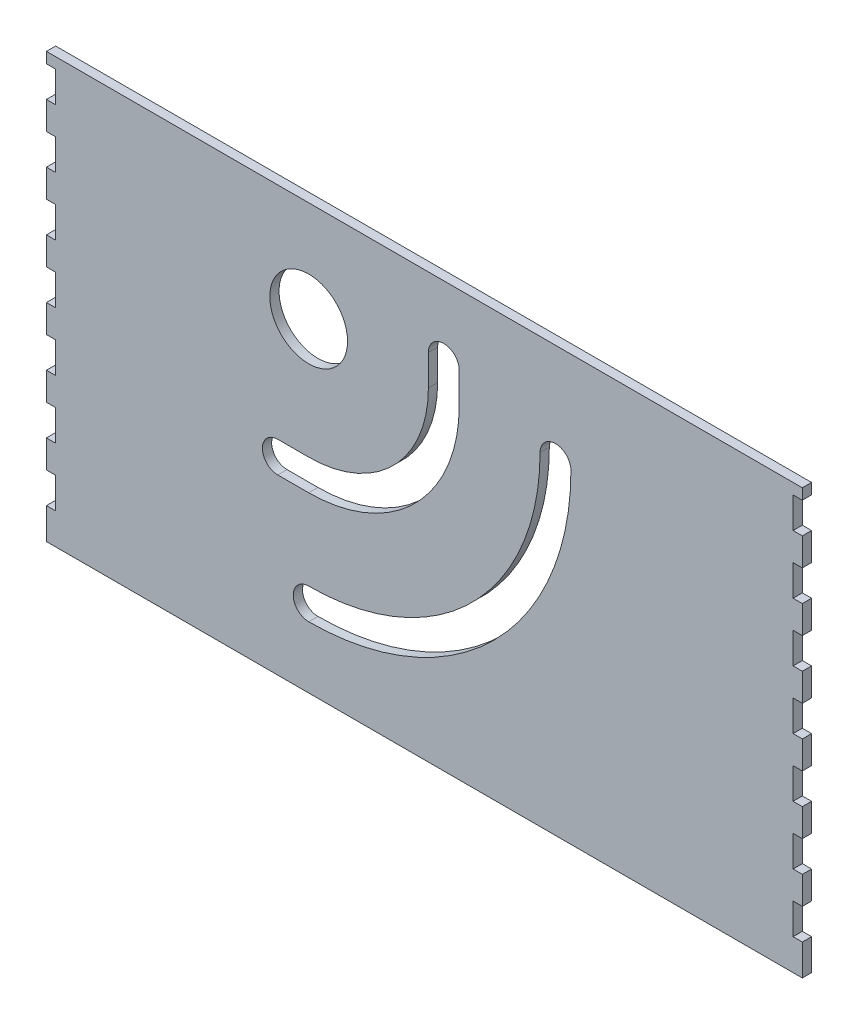
SolidWorks part; units mm, degrees
material "birch 3mm plywood"
ref_plane "Front Plane" through (0, 0, 0) normal (0, 0, 1) x (1, 0, 0)
ref_plane "Top Plane" through (0, 0, 0) normal (0, 1, 0) x (1, 0, 0)
ref_plane "Right Plane" through (0, 0, 0) normal (1, 0, 0) x (0, 0, -1)
sketch "Sketch1" plane through (0, 0, 0) normal (0, 0, 1) x (1, 0, 0)
  line L0 (244.5, 137.6) -> (244.5, 134.1)
  line L1 (-0.5, 137.6) -> (244.5, 137.6)
  line L2 (-0.5, 137.6) -> (-0.5, 0) construction
  line L3 (-0.5, 0) -> (244.5, 0)
  line L4 (244.5, 137.6) -> (244.5, 0) construction
  line L5 (84.5, 59.75) -> (84.5, -77.75) construction
  line L6 (244.5, 134.1) -> (241.5, 134.1)
  line L7 (241.5, 134.1) -> (241.5, 124.1)
  line L8 (241.5, 124.1) -> (244.5, 124.1)
  line L9 (244.5, 124.1) -> (244.5, 115.1)
  line L10 (244.5, 105.1) -> (244.5, 96.1)
  line L11 (241.5, 115.1) -> (241.5, 105.1)
  line L12 (241.5, 105.1) -> (244.5, 105.1)
  line L13 (244.5, 115.1) -> (241.5, 115.1)
  line L14 (244.5, 86.1) -> (244.5, 77.1)
  line L15 (241.5, 96.1) -> (241.5, 86.1)
  line L16 (241.5, 86.1) -> (244.5, 86.1)
  line L17 (244.5, 96.1) -> (241.5, 96.1)
  line L18 (244.5, 67.1) -> (244.5, 58.1)
  line L19 (241.5, 77.1) -> (241.5, 67.1)
  line L20 (241.5, 67.1) -> (244.5, 67.1)
  line L21 (244.5, 77.1) -> (241.5, 77.1)
  line L22 (244.5, 48.1) -> (244.5, 39.1)
  line L23 (241.5, 58.1) -> (241.5, 48.1)
  line L24 (241.5, 48.1) -> (244.5, 48.1)
  line L25 (244.5, 58.1) -> (241.5, 58.1)
  line L26 (244.5, 29.1) -> (244.5, 20.1)
  line L27 (241.5, 39.1) -> (241.5, 29.1)
  line L28 (241.5, 29.1) -> (244.5, 29.1)
  line L29 (244.5, 39.1) -> (241.5, 39.1)
  line L30 (244.5, 10.1) -> (244.5, 0)
  line L31 (241.5, 20.1) -> (241.5, 10.1)
  line L32 (241.5, 10.1) -> (244.5, 10.1)
  line L33 (244.5, 20.1) -> (241.5, 20.1)
  line L34 (122, 137.6) -> (122, 0) construction
  line L35 (-0.5, 10.1) -> (-0.5, 0)
  line L36 (-0.5, 20.1) -> (2.5, 20.1)
  line L37 (2.5, 10.1) -> (-0.5, 10.1)
  line L38 (2.5, 20.1) -> (2.5, 10.1)
  line L39 (-0.5, 39.1) -> (2.5, 39.1)
  line L40 (2.5, 29.1) -> (-0.5, 29.1)
  line L41 (2.5, 39.1) -> (2.5, 29.1)
  line L42 (-0.5, 29.1) -> (-0.5, 20.1)
  line L43 (-0.5, 58.1) -> (2.5, 58.1)
  line L44 (2.5, 48.1) -> (-0.5, 48.1)
  line L45 (2.5, 58.1) -> (2.5, 48.1)
  line L46 (-0.5, 48.1) -> (-0.5, 39.1)
  line L47 (-0.5, 77.1) -> (2.5, 77.1)
  line L48 (2.5, 67.1) -> (-0.5, 67.1)
  line L49 (2.5, 77.1) -> (2.5, 67.1)
  line L50 (-0.5, 67.1) -> (-0.5, 58.1)
  line L51 (-0.5, 96.1) -> (2.5, 96.1)
  line L52 (2.5, 86.1) -> (-0.5, 86.1)
  line L53 (2.5, 96.1) -> (2.5, 86.1)
  line L54 (-0.5, 86.1) -> (-0.5, 77.1)
  line L55 (-0.5, 115.1) -> (2.5, 115.1)
  line L56 (2.5, 105.1) -> (-0.5, 105.1)
  line L57 (2.5, 115.1) -> (2.5, 105.1)
  line L58 (-0.5, 105.1) -> (-0.5, 96.1)
  line L59 (-0.5, 124.1) -> (-0.5, 115.1)
  line L60 (2.5, 124.1) -> (-0.5, 124.1)
  line L61 (2.5, 134.1) -> (2.5, 124.1)
  line L62 (-0.5, 134.1) -> (2.5, 134.1)
  line L63 (-0.5, 137.6) -> (-0.5, 134.1)
  line L64 (93.4095, 96.0905) -> (137.533, 51.967) construction
  line L65 (111.9357, 77.5643) -> (119.0068, 70.4932) construction
  line L66 (123.3, 105) -> (123.3, 115)
  line L68 (133.3, 115) -> (133.3, 105)
  line L69 (84.5, 66.2) -> (74.5, 66.2)
  line L71 (74.5, 56.2) -> (84.5, 56.2)
  arc A0 (84.5, 66.2) -> (123.3, 105) centre (84.5, 105) ccw
  arc A1 (84.5, 56.2) -> (133.3, 105) centre (84.5, 105) ccw
  arc A3 (169.5, 105) -> (159.5, 105) centre (164.5, 105) ccw
  arc A4 (159.5, 105) -> (84.5, 30) centre (84.5, 105) cw
  arc A5 (169.5, 105) -> (84.5, 20) centre (84.5, 105) cw
  arc A6 (84.5, 20) -> (84.5, 30) centre (84.5, 25) cw
  circle A7 centre (84.5, 105) radius 12.6
  arc A8 (123.3, 115) -> (133.3, 115) centre (128.3, 115) cw
  arc A9 (74.5, 56.2) -> (74.5, 66.2) centre (74.5, 61.2) cw
  point P77 (137.533, 51.967)
  point P80 (115.4713, 74.0287)
  point P89 (0, 0)
  point P90 (133.3, 120.0897)
  point P91 (133.3, 116.1836)
  point P92 (133.3, 114.8816)
  dimension "D1" = 10
  dimension "D2" = 75
  dimension "D3" = 20
  dimension "D7" = 25.2
  dimension "D15" = 10
  dimension "D4" = 20
  dimension "D5" = 85
  dimension "D6" = 160
  dimension "D8" = 3.5
  dimension "D9" = 10
  dimension "D10" = 9
  dimension "D12" = 3
  dimension "D13" = 10
  dimension "D14" = 5
  dimension "D11" = 7
extrude "Boss-Extrude1" add sketch "Sketch1" along normal blind 3
